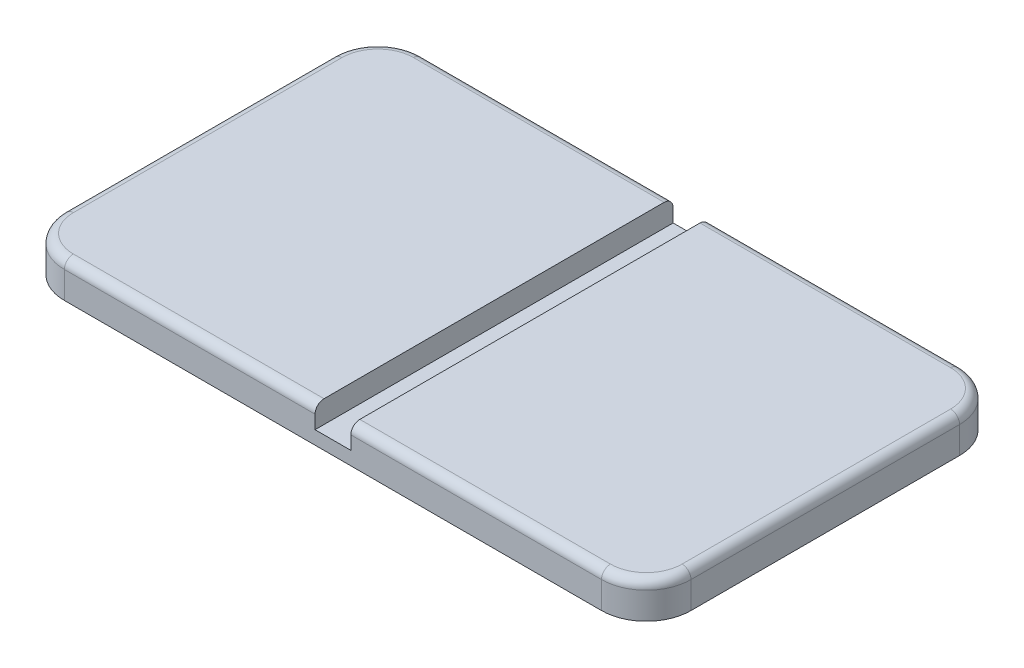
SolidWorks part; units mm, degrees
ref_plane "Front Plane" through (0, 0, 0) normal (0, 0, 1) x (1, 0, 0)
ref_plane "Top Plane" through (0, 0, 0) normal (0, 1, 0) x (1, 0, 0)
ref_plane "Right Plane" through (0, 0, 0) normal (1, 0, 0) x (0, 0, -1)
sketch "Sketch1" plane through (0, 0, 0) normal (0, 1, 0) x (1, 0, 0)
  line L1 (-60, -40) -> (60, -40)
  line L2 (-70, -30) -> (-70, 30)
  line L3 (-60, 40) -> (60, 40)
  line L4 (70, -30) -> (70, 30)
  line L5 (-70, -40) -> (70, 40) construction
  line L6 (-70, 40) -> (70, -40) construction
  line L7 (4, 40) -> (-4, 40)
  line L8 (4, 40) -> (4, -40)
  line L9 (4, -40) -> (-4, -40)
  line L10 (-4, 40) -> (-4, -40)
  line L11 (4, 40) -> (-4, -40) construction
  line L12 (4, -40) -> (-4, 40) construction
  arc A0 (60, 40) -> (70, 30) centre (60, 30) cw
  arc A1 (-70, -30) -> (-60, -40) centre (-60, -30) ccw
  arc A2 (70, -30) -> (60, -40) centre (60, -30) cw
  arc A3 (-60, 40) -> (-70, 30) centre (-60, 30) ccw
  point P0 (0, 0)
  point P18 (0, 0)
  dimension "D1" = 10
  dimension "D2" = 10
  dimension "D3" = 8
  dimension "D4" = 140
  dimension "D5" = 80
extrude "Boss-Extrude1" add sketch "Sketch1" along normal blind 3 contours L3 L10 L1 L8 region at (0, 0, 0)
extrude "Boss-Extrude2" add sketch "Sketch1<3>" along normal blind 8 contours L3 A3 L2 A1 L1 L10 | A2 L4 A0 L3 L8 L1 region at (-36.7479, 0, 0) region at (36.7479, 0, 0)
sketch "Sketch1<3>" plane through (0, 0, 0) normal (0, 1, 0) x (1, 0, 0) same geometry as "Sketch1"
fillet "Fillet1" radius 2 10 edges at (-32, 8, 40) (-67.0711, 8, 37.0711) (-32, 8, -40) (-67.0711, 8, -37.0711) (32, 8, 40) (32, 8, -40) (67.0711, 8, -37.0711) (70, 8, 0) (67.0711, 8, 37.0711) (-70, 8, 0)
